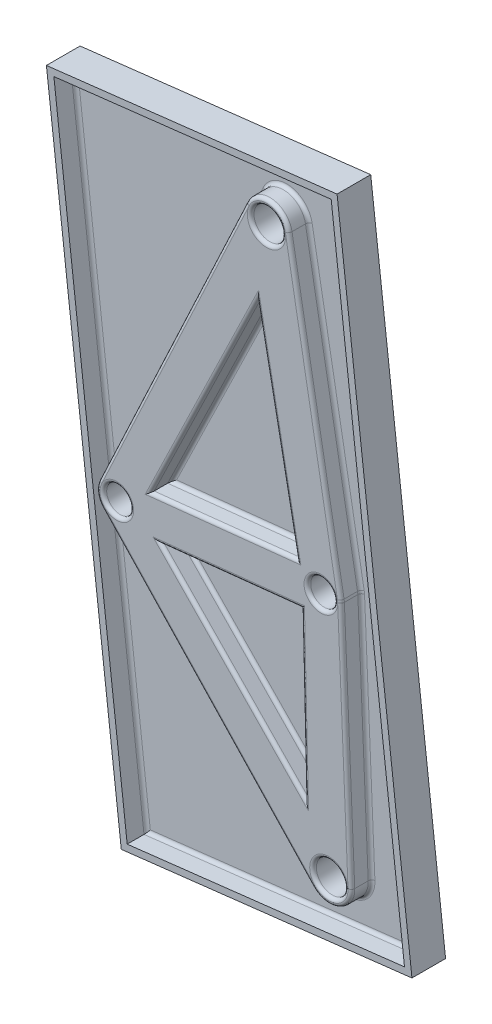
SolidWorks part; units mm, degrees
ref_plane "Plan de face" through (0, 0, 0) normal (0, 0, 1) x (1, 0, 0)
ref_plane "Plan de dessus" through (0, 0, 0) normal (0, 1, 0) x (1, 0, 0)
ref_plane "Plan de droite" through (0, 0, 0) normal (1, 0, 0) x (0, 0, -1)
sketch "Esquisse1" plane through (0, 0, 0) normal (0, 0, 1) x (1, 0, 0)
  line L1 (31.3699, 56.4746) -> (-11.8368, 51.4319)
  line L4 (44.3534, -54.7703) -> (29.5151, 72.3667)
  line L5 (29.5151, 72.3667) -> (24.0522, 71.7291)
  line L6 (-13.6916, 67.324) -> (1.1466, -59.813)
  line L7 (38.8904, -55.4079) -> (44.3534, -54.7703)
  line L8 (42.4986, -38.8782) -> (31.3699, 56.4746)
  line L10 (-11.8368, 51.4319) -> (-0.7082, -43.9209)
  line L11 (-0.7082, -43.9209) -> (42.4986, -38.8782)
  line L20 (24.0522, 71.7291) -> (25.907, 55.837)
  line L22 (25.907, 55.837) -> (-1.9043, 52.5911)
  line L24 (-1.9043, 52.5911) -> (-3.759, 68.4833)
  line L26 (-3.759, 68.4833) -> (-13.6916, 67.324)
  line L28 (1.1466, -59.813) -> (13.0657, -58.4219)
  line L30 (13.0657, -58.4219) -> (11.2109, -42.5298)
  line L32 (11.2109, -42.5298) -> (37.0357, -39.5158)
  line L34 (37.0357, -39.5158) -> (38.8904, -55.4079)
  circle A0 centre (-1.3739, 0.602) radius 2 construction
  circle A1 centre (-1.3739, 0.602) radius 2
  circle A2 centre (28.9566, 3.8285) radius 2 construction
  circle A3 centre (28.9566, 3.8285) radius 2
  circle A4 centre (20.8748, 47.1954) radius 2.35 construction
  circle A5 centre (20.8748, 47.1954) radius 2.35
  circle A9 centre (30.1487, -32.2653) radius 2.35 construction
  circle A10 centre (30.1487, -32.2653) radius 2.35
  dimension "D1" = 0
extrude "Boss.-Extru.1" add sketch "Esquisse1" along normal blind 5
sketch "Esquisse3" plane through (0, 0, 5) normal (0, 0, 1) x (1, 0, 0)
  line L4 (0.1692, -42.8117) -> (41.3894, -38.0009)
  line L5 (0.1692, -42.8117) -> (41.3894, -38.0009)
  line L6 (30.4926, 55.3654) -> (-10.7277, 50.5546)
  line L7 (30.4926, 55.3654) -> (-10.7277, 50.5546)
  line L25 (41.3894, -38.0009) -> (30.4926, 55.3654)
  line L31 (-10.7277, 50.5546) -> (0.1692, -42.8117)
  line L37 (41.3894, -38.0009) -> (30.4926, 55.3654)
  line L43 (-10.7277, 50.5546) -> (0.1692, -42.8117)
  dimension "D1" = 1
extrude "Enlèv. mat.-Extru.1" cut sketch "Esquisse3" against normal blind 3
sketch "Esquisse4" plane through (0, 0, 2) normal (0, 0, 1) x (1, 0, 0)
  circle A0 centre (-1.3739, 0.602) radius 2 construction
  circle A1 centre (-1.3739, 0.602) radius 2
  circle A2 centre (28.9566, 3.8285) radius 2 construction
  circle A3 centre (28.9566, 3.8285) radius 2
  circle A4 centre (20.8748, 47.1954) radius 2.35 construction
  circle A5 centre (30.1487, -32.2653) radius 2.35 construction
  circle A6 centre (20.8748, 47.1954) radius 2.35
  circle A7 centre (30.1487, -32.2653) radius 2.35
  circle A8 centre (-1.3739, 0.602) radius 3
  circle A9 centre (30.1487, -32.2653) radius 3.35
  circle A10 centre (28.9566, 3.8285) radius 3
  circle A11 centre (20.8748, 47.1954) radius 3.35
  dimension "D1" = 1
  dimension "D2" = 1
extrude "Boss.-Extru.3" add sketch "Esquisse4" along normal blind 3
sketch "Esquisse5" plane through (0, 0, 2) normal (0, 0, 1) x (1, 0, 0)
  line L2 (27.7132, -34.5654) -> (-3.5549, -1.4579)
  line L4 (0.7752, 2.6951) -> (32.5486, -29.9279)
  circle A1 centre (-1.3739, 0.602) radius 3 construction
  arc A3 (-3.5549, -1.4579) -> (0.7752, 2.6951) centre (-1.3739, 0.602) ccw
  circle A4 centre (30.1487, -32.2653) radius 3.35 construction
  arc A5 (32.5486, -29.9279) -> (27.7132, -34.5654) centre (30.1487, -32.2653) ccw
extrude "Boss.-Extru.4" add sketch "Esquisse5" along normal blind 3
sketch "Esquisse6" plane through (0, 0, 2) normal (0, 0, 1) x (1, 0, 0)
  line L0 (33.4957, -32.1222) -> (31.9538, 3.9566)
  line L1 (26.7996, -32.3434) -> (26.0334, 0.5006)
  line L2 (31.9538, 3.9566) -> (31.91, 4.3547)
  line L3 (-1.0566, -2.3812) -> (26.0334, 0.5006)
  line L4 (3.6889, 4.1575) -> (25.3871, 6.4657)
  line L5 (25.3871, 6.4657) -> (19.503, 36.7061)
  line L6 (-4.0898, 1.8763) -> (17.8421, 48.6184)
  line L7 (24.1729, 47.783) -> (31.91, 4.3547)
  line L8 (3.6889, 4.1575) -> (19.503, 36.7061)
  circle A0 centre (28.9566, 3.8285) radius 2 construction
  arc A1 (0.7752, 2.6951) -> (-3.5549, -1.4579) centre (-1.3739, 0.602) ccw construction
  arc A2 (-1.0566, -2.3812) -> (-4.0898, 1.8763) centre (-1.3739, 0.602) ccw
  arc A3 (27.7132, -34.5654) -> (32.5486, -29.9279) centre (30.1487, -32.2653) ccw construction
  circle A4 centre (20.8748, 47.1954) radius 3.35 construction
  arc A6 (33.4957, -32.1222) -> (26.7996, -32.3434) centre (30.1487, -32.2653) ccw
  arc A7 (17.8421, 48.6184) -> (24.1729, 47.783) centre (20.8748, 47.1954) ccw
  circle A8 centre (28.9566, 3.8285) radius 2 construction
  circle A9 centre (20.8748, 47.1954) radius 2.35 construction
  circle A10 centre (20.8748, 47.1954) radius 2.35 construction
  circle A11 centre (28.9566, 3.8285) radius 2.5
  dimension "D1" = 36.187
  dimension "D2" = 8.0792
  dimension "D3" = 36.0788
  dimension "D4" = 43.4283
  dimension "D5" = 32.844
  dimension "D6" = 27.0899
  dimension "D7" = 30.2404
  dimension "D8" = 21.6982
  dimension "D9" = 0.3981
  dimension "D10" = 151.64
  dimension "D11" = 27.584
  dimension "D12" = 0.5
extrude "Boss.-Extru.7" add sketch "Esquisse6" along normal blind 3
fillet "Congé1" radius 0.5 18 edges at (32.4987, -32.2653, 5) (0.6261, 0.602, 5) (30.9566, 3.8285, 5) (23.2248, 47.1954, 5) (22.4451, 21.5859, 5) (11.5959, 20.4318, 5) (14.538, 5.3116, 5) (15.5583, -0.6137, 5) (15.842, -12.7746, 5) (26.3171, -11.6602, 5) (21.3131, 50.5166, 5) (28.0415, 26.0688, 5) (31.9386, 4.1564, 5) (32.7247, -14.0828, 5) (31.4526, -35.3511, 5) (12.0791, -18.0117, 5) (-4.336, 0.1268, 5) (6.8761, 25.2474, 5)
fillet "Congé2" radius 0.5 3 edges at (22.4451, 21.5859, 2) (14.538, 5.3116, 2) (11.5959, 20.4318, 2)
fillet "Congé3" radius 0.5 3 edges at (15.842, -12.7746, 2) (15.5583, -0.6137, 2) (26.3171, -11.6602, 2)
fillet "Congé4" radius 0.5 12 edges at (28.0415, 26.0688, 2) (21.3131, 50.5166, 2) (6.8761, 25.2474, 2) (-4.336, 0.1268, 2) (12.0791, -18.0117, 2) (31.4526, -35.3511, 2) (32.7247, -14.0828, 2) (31.9386, 4.1564, 2) (-5.2792, 3.8714, 2) (35.941, 8.6823, 2) (20.7793, -40.4063, 2) (9.8824, 52.96, 2)
